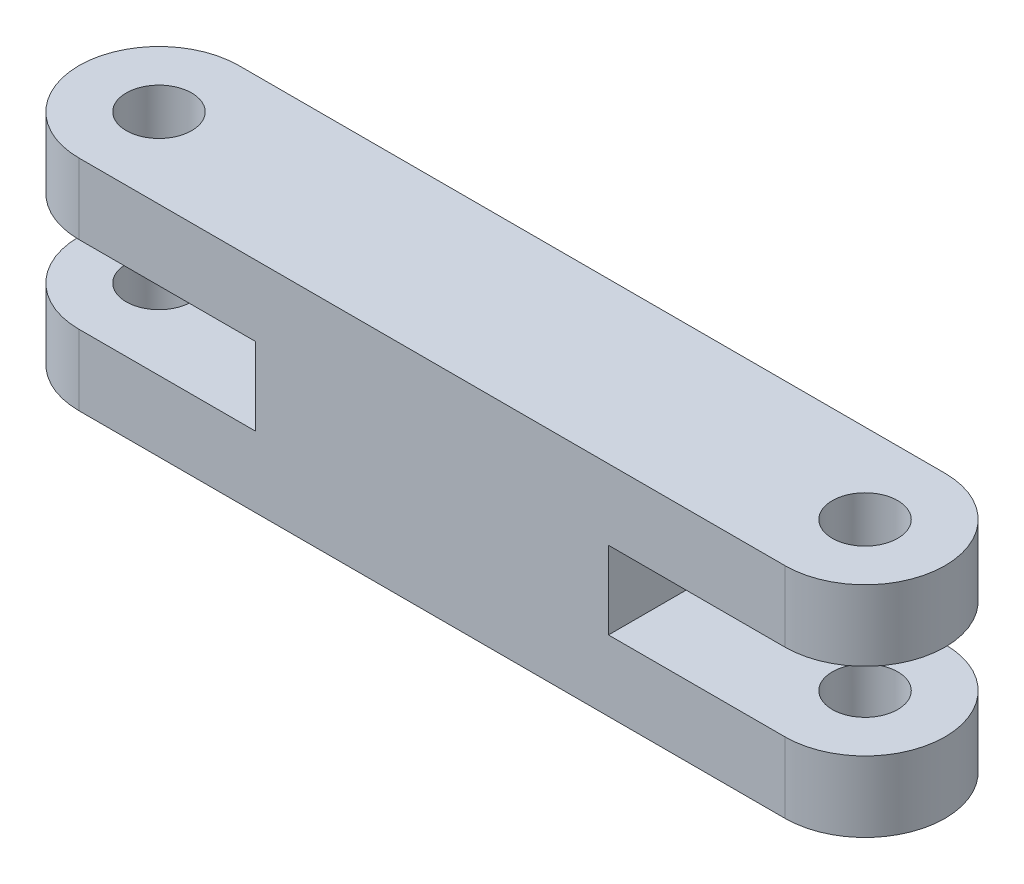
SolidWorks part; units mm, degrees
ref_plane "Front Plane" through (0, 0, 0) normal (0, 0, 1) x (1, 0, 0)
ref_plane "Top Plane" through (0, 0, 0) normal (0, 1, 0) x (1, 0, 0)
ref_plane "Right Plane" through (0, 0, 0) normal (1, 0, 0) x (0, 0, -1)
sketch "Sketch1" plane through (0, 0, 0) normal (0, 0, 1) x (1, 0, 0)
  line L0 (3.4, -9.3) -> (3.4, 0)
  line L1 (3.4, 0) -> (33.4, 0)
  line L2 (33.4, 0) -> (33.4, -9.3)
  line L3 (33.4, -9.3) -> (3.4, -9.3)
extrude "Boss-Extrude2" add sketch "Sketch1" along normal blind 3.4 and the other way blind 3.4
sketch "Sketch3" plane through (0, 0, 3.4) normal (0, 0, 1) x (1, 0, 0)
  line L0 (3.4, -3) -> (3.4, -6.3)
  line L1 (3.4, -3) -> (10.9, -3)
  line L2 (3.4, -6.3) -> (10.9, -6.3)
  line L3 (10.9, -3) -> (10.9, -6.3)
extrude "Cut-Extrude1" cut sketch "Sketch3" against normal blind 6.8 contours L0 L2 L3 L1
sketch "Sketch4" plane through (0, 0, 3.4) normal (0, 0, 1) x (1, 0, 0)
  line L0 (33.4, -3) -> (33.4, -6.3)
  line L1 (33.4, -3) -> (25.9, -3)
  line L2 (33.4, -6.3) -> (25.9, -6.3)
  line L3 (25.9, -3) -> (25.9, -6.3)
extrude "Cut-Extrude2" cut sketch "Sketch4" against normal blind 6.8 contours L0 L2 L3 L1
sketch "Sketch5" plane through (0, 0, 0) normal (0, 1, 0) x (1, 0, 0)
  line L0 (3.4, 3.4) -> (3.4, -3.4)
  arc A0 (3.4, 3.4) -> (3.4, -3.4) centre (3.4, 0) ccw
extrude "Boss-Extrude3" add sketch "Sketch5" against normal up to vertex (3 mm away) up to point (3.4, -3, -3.4)
sketch "Sketch6" plane through (0, 0, 0) normal (0, 1, 0) x (1, 0, 0)
  line L0 (33.4, 3.4) -> (33.4, -3.4)
  arc A0 (33.4, 3.4) -> (33.4, -3.4) centre (33.4, 0) cw
extrude "Boss-Extrude4" add sketch "Sketch6" against normal up to vertex (3 mm away) up to point (33.4, -3, -3.4)
sketch "Sketch7" plane through (0, -9.3, 0) normal (0, -1, 0) x (-1, 0, 0)
  line L0 (-3.4, -3.4) -> (-3.4, 3.4)
  arc A0 (-3.4, -3.4) -> (-3.4, 3.4) centre (-3.4, 0) ccw
extrude "Boss-Extrude5" add sketch "Sketch7" against normal up to vertex (3 mm away) up to point (3.4, -6.3, 3.4)
sketch "Sketch8" plane through (0, -9.3, 0) normal (0, -1, 0) x (-1, 0, 0)
  line L0 (-33.4, -3.4) -> (-33.4, 3.4)
  arc A0 (-33.4, -3.4) -> (-33.4, 3.4) centre (-33.4, 0) cw
extrude "Boss-Extrude6" add sketch "Sketch8" against normal up to vertex (3 mm away) up to point (33.4, -6.3, -3.4)
sketch "Sketch9" plane through (0, 0, 0) normal (0, 1, 0) x (1, 0, 0)
  circle A0 centre (3.4, 0) radius 1.39
extrude "Cut-Extrude3" cut sketch "Sketch9" against normal up to vertex (9.3 mm away) up to point (3.4, -9.3, 3.4)
sketch "Sketch10" plane through (0, 0, 0) normal (0, 1, 0) x (1, 0, 0)
  circle A0 centre (33.4, 0) radius 1.39
extrude "Cut-Extrude4" cut sketch "Sketch10" against normal up to vertex (9.3 mm away) up to point (33.4, -9.3, -3.4)
